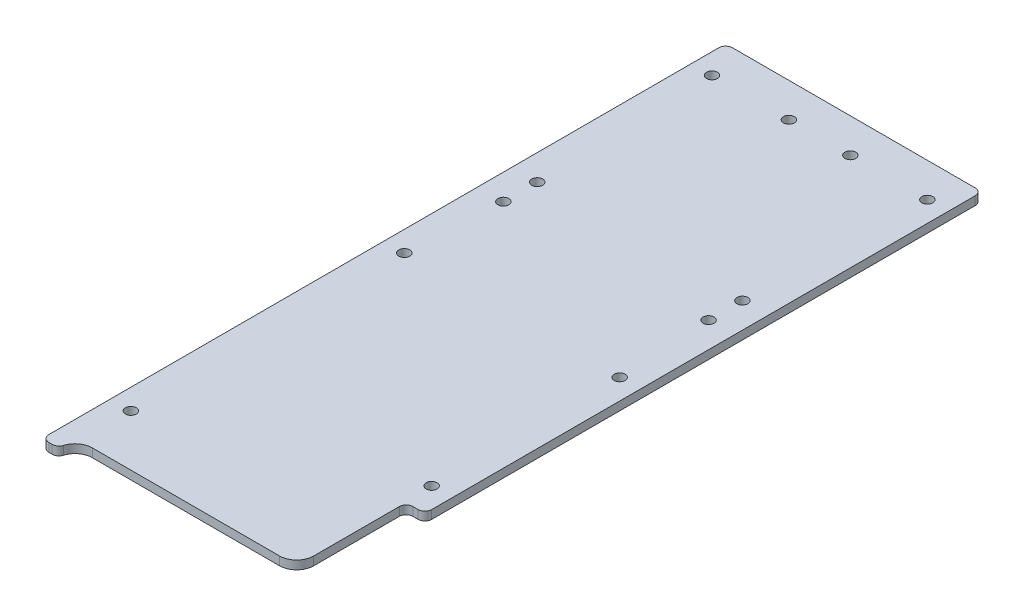
SolidWorks part; units mm, degrees
ref_plane "Front Plane" through (0, 0, 0) normal (0, 0, 1) x (1, 0, 0)
ref_plane "Top Plane" through (0, 0, 0) normal (0, 1, 0) x (1, 0, 0)
ref_plane "Right Plane" through (0, 0, 0) normal (1, 0, 0) x (0, 0, -1)
sketch "Sketch1" plane through (0, 0, 0) normal (0, 1, 0) x (1, 0, 0)
  line L0 (-39.9997, 0) -> (-39.9997, 114.3) construction
  line L1 (-47.625, 127) -> (47.625, 127)
  line L2 (-47.625, 127) -> (-47.625, -127)
  line L3 (-47.625, -127) -> (47.625, -127)
  line L4 (47.625, 127) -> (47.625, -127)
  line L5 (-47.625, 127) -> (47.625, -127) construction
  line L6 (-47.625, -127) -> (47.625, 127) construction
  line L7 (0, 0) -> (0, 127) construction
  line L8 (-39.9997, 0) -> (-39.9997, -101.6) construction
  line L9 (-39.9997, 0) -> (0, 0) construction
  line L10 (-41.275, -127) -> (-41.275, -120.65)
  line L11 (-41.275, -120.65) -> (41.275, -120.65)
  line L12 (41.275, -120.65) -> (41.275, -127)
  line L13 (-39.9997, 114.3) -> (-11.4247, 114.3) construction
  line L14 (39.9997, 114.3) -> (11.4247, 114.3) construction
  circle A0 centre (-39.9997, 114.3) radius 2.032
  circle A1 centre (-39.9997, 0) radius 2.032
  circle A2 centre (-39.9997, -101.6) radius 2.032
  circle A3 centre (39.9997, -101.6) radius 2.032
  circle A4 centre (39.9997, 0) radius 2.032
  circle A5 centre (39.9997, 114.3) radius 2.032
  circle A6 centre (-11.4247, 114.3) radius 2.032
  circle A7 centre (11.4247, 114.3) radius 2.032
  circle A8 centre (-39.9997, -69.85) radius 2.032
  circle A9 centre (39.9997, -69.85) radius 2.032
  point P0 (0, 0)
  dimension "D4" = 4.064
  dimension "D10" = 28.575
  dimension "D1" = 95.25
  dimension "D2" = 254
  dimension "D3" = 7.6253
  dimension "D5" = 12.7
  dimension "D6" = 25.4
  dimension "D7" = 6.35
  dimension "D8" = 6.35
  dimension "D9" = 6.35
  dimension "D11" = 69.85
extrude "Boss-Extrude1" add sketch "Sketch1" along normal blind 3.175 contours L4 L1 L2 L3 A4 A0 A1 A2 A3 A5 | A8 | A3 region at (0, 0, -2.6944) region at (39.9997, 0, 101.6) region at (-39.9997, 0, 69.85)
fillet "Fillet1" radius 2.54 4 edges at (-47.625, 1.5875, -127) (47.625, 1.5875, -127) (47.625, 1.5875, 127) (-47.625, 1.5875, 127)
fillet "Fillet2" radius 2.54 2 edges at (41.275, 1.5875, 127) (-41.275, 1.5875, 127)
fillet "Fillet3" radius 6.35 2 edges at (41.275, 1.5875, 120.65) (-41.275, 1.5875, 120.65)
sketch "Sketch2" plane through (0, 0, 0) normal (0, -1, 0) x (1, 0, 0)
  line L0 (41.9104, 131.8831) -> (41.9104, 109.8659) construction
  line L1 (41.9104, 109.8659) -> (41.9104, 106.3879) construction
  line L2 (41.9104, 83.271) -> (41.9104, 82.5325) construction
  line L3 (41.9104, 82.5325) -> (41.9104, 81.2514) construction
  line L4 (41.9104, 83.271) -> (41.9104, 106.3879) construction
  line L5 (41.9104, 131.8831) -> (41.9104, 109.8659)
  line L6 (41.9104, 109.8659) -> (41.9104, 106.3879)
  line L7 (41.9104, 83.271) -> (41.9104, 82.5325)
  line L8 (41.9104, 82.5325) -> (41.9104, 81.2514)
  line L9 (41.9104, 83.271) -> (41.9104, 106.3879)
  line L10 (41.9104, 81.2514) -> (47.625, 81.2514)
  line L11 (47.625, -124.46) -> (47.625, 124.46) construction
  line L12 (41.9104, 131.8831) -> (47.625, 131.8831)
  line L13 (47.625, 131.8831) -> (47.625, 81.2514)
  line L14 (40.6404, 79.9814) -> (48.895, 79.9814)
  line L15 (48.895, 133.1531) -> (48.895, 79.9814)
  line L16 (40.6404, 133.1531) -> (48.895, 133.1531)
  line L17 (40.6404, 133.1531) -> (40.6404, 109.8659)
  line L18 (40.6404, 109.8659) -> (40.6404, 106.3879)
  line L19 (40.6404, 83.271) -> (40.6404, 106.3879)
  line L20 (40.6404, 83.271) -> (40.6404, 82.5325)
  line L21 (40.6404, 82.5325) -> (40.6404, 79.9814)
  arc M7 (43.815, 127) -> (41.3809, 125.1857) centre (43.815, 124.46) ccw
  arc M8 (41.3809, 125.1857) -> (35.2956, 120.65) centre (35.2956, 127) cw
  line M18 (47.625, -124.46) -> (47.625, 124.46)
  dimension "D1" = 1.27
extrude "Cut-Extrude1" cut sketch "Sketch2" against normal through all contours L20 L21 L14 L10 L8 L7 L9 L19 M18 | L19 L9 L6 L5 L17 L18 M7 M8 | L13 L10 L8 L7 L9 L6 L5 L12 region at (41.6755, 0, 99.9793)
fillet "Fillet4" radius 6.35 1 edges at (40.6404, 1.5875, 123.5714)
fillet "Fillet5" radius 2.54 2 edges at (47.625, 1.5875, 79.9814) (40.6404, 1.5875, 79.9814)
sketch "Sketch3" plane through (0, 0, 0) normal (0, -1, 0) x (1, 0, 0)
  line L0 (-36.3101, -49.7791) -> (-39.9169, -49.7791) construction
  line L1 (-40.4249, -49.276) -> (-40.4249, -45.7043) construction
  line L2 (-35.8021, -45.7043) -> (-35.8021, -49.276) construction
  line L3 (-39.9169, -45.2013) -> (-36.3101, -45.2013) construction
  line L4 (-36.3101, -37.2027) -> (-39.9169, -37.2027) construction
  line L5 (-35.8021, -33.1279) -> (-35.8021, -36.6996) construction
  line L6 (-40.4249, -36.6996) -> (-40.4249, -33.1279) construction
  line L7 (-39.9169, -32.6249) -> (-36.3101, -32.6249) construction
  line L8 (36.2831, -32.6249) -> (39.8899, -32.6249) construction
  line L9 (40.3979, -33.1279) -> (40.3979, -36.6996) construction
  line L10 (39.8899, -37.2027) -> (36.2831, -37.2027) construction
  line L11 (35.7751, -36.6996) -> (35.7751, -33.1279) construction
  line L12 (36.2831, -45.2013) -> (39.8899, -45.2013) construction
  line L13 (35.7751, -49.276) -> (35.7751, -45.7043) construction
  line L14 (40.3979, -45.7043) -> (40.3979, -49.276) construction
  line L15 (39.8899, -49.7791) -> (36.2831, -49.7791) construction
  line L16 (-36.3101, -49.7791) -> (-39.9169, -49.7791)
  line L17 (-40.4249, -49.276) -> (-40.4249, -45.7043)
  line L18 (-35.8021, -45.7043) -> (-35.8021, -49.276)
  line L19 (-39.9169, -45.2013) -> (-36.3101, -45.2013)
  line L20 (-36.3101, -37.2027) -> (-39.9169, -37.2027)
  line L21 (-35.8021, -33.1279) -> (-35.8021, -36.6996)
  line L22 (-40.4249, -36.6996) -> (-40.4249, -33.1279)
  line L23 (-39.9169, -32.6249) -> (-36.3101, -32.6249)
  line L24 (36.2831, -32.6249) -> (39.8899, -32.6249)
  line L25 (40.3979, -33.1279) -> (40.3979, -36.6996)
  line L26 (39.8899, -37.2027) -> (36.2831, -37.2027)
  line L27 (35.7751, -36.6996) -> (35.7751, -33.1279)
  line L28 (36.2831, -45.2013) -> (39.8899, -45.2013)
  line L29 (35.7751, -49.276) -> (35.7751, -45.7043)
  line L30 (40.3979, -45.7043) -> (40.3979, -49.276)
  line L31 (39.8899, -49.7791) -> (36.2831, -49.7791)
  line L32 (-47.625, -25.836) -> (47.625, -25.836)
  line L33 (-47.625, -124.46) -> (-47.625, 124.46) construction
  line L34 (47.625, -124.46) -> (47.625, 77.4414) construction
  line L35 (0, -25.836) -> (0, -56.0686) construction
  line L38 (134.3607, -51.414) -> (184.1365, -51.414)
  line L39 (184.1365, -51.414) -> (184.1365, -43.4909)
  line L40 (184.1365, -43.4909) -> (182.3331, -43.4909)
  line L41 (181.8251, -42.9878) -> (181.8251, -39.4161)
  line L42 (182.3331, -38.9131) -> (184.1365, -38.9131)
  line L43 (184.1365, -38.9131) -> (184.1365, -30.9899)
  line L44 (184.1365, -30.9899) -> (134.3607, -30.9899)
  line L45 (134.3607, -30.9899) -> (133.3365, -32.0042)
  line L46 (133.3365, -32.0042) -> (132.3123, -30.9899)
  line L47 (132.3123, -30.9899) -> (70.8607, -30.9899)
  line L48 (70.8607, -30.9899) -> (69.8365, -32.0042)
  line L49 (69.8365, -32.0042) -> (68.8123, -30.9899)
  line L50 (68.8123, -30.9899) -> (7.3607, -30.9899)
  line L51 (7.3607, -30.9899) -> (6.3365, -32.0042)
  line L52 (6.3365, -32.0042) -> (5.3123, -30.9899)
  line L53 (5.3123, -30.9899) -> (-56.1393, -30.9899)
  line L54 (-56.1393, -30.9899) -> (-57.1635, -32.0042)
  line L55 (-57.1635, -32.0042) -> (-58.1877, -30.9899)
  line L56 (-58.1877, -30.9899) -> (-119.6393, -30.9899)
  line L57 (-119.6393, -30.9899) -> (-120.6635, -32.0042)
  line L58 (-120.6635, -32.0042) -> (-121.6877, -30.9899)
  line L59 (-121.6877, -30.9899) -> (-184.1635, -30.9899)
  line L60 (-184.1635, -30.9899) -> (-184.1635, -51.414)
  line L61 (-184.1635, -51.414) -> (-121.6877, -51.414)
  line L62 (-121.6877, -51.414) -> (-120.6635, -50.3998)
  line L63 (-120.6635, -50.3998) -> (-119.6393, -51.414)
  line L64 (-119.6393, -51.414) -> (-58.1877, -51.414)
  line L65 (-58.1877, -51.414) -> (-57.1635, -50.3998)
  line L66 (-57.1635, -50.3998) -> (-56.1393, -51.414)
  line L67 (-56.1393, -51.414) -> (5.3123, -51.414)
  line L68 (5.3123, -51.414) -> (6.3365, -50.3998)
  line L69 (6.3365, -50.3998) -> (7.3607, -51.414)
  line L70 (7.3607, -51.414) -> (68.8123, -51.414)
  line L71 (68.8123, -51.414) -> (69.8365, -50.3998)
  line L72 (69.8365, -50.3998) -> (70.8607, -51.414)
  line L73 (70.8607, -51.414) -> (132.3123, -51.414)
  line L74 (132.3123, -51.414) -> (133.3365, -50.3998)
  line L75 (133.3365, -50.3998) -> (134.3607, -51.414)
  line L76 (134.3607, -51.414) -> (184.1365, -51.414)
  line L77 (184.1365, -51.414) -> (184.1365, -43.4909)
  line L78 (184.1365, -43.4909) -> (182.3331, -43.4909)
  line L79 (181.8251, -42.9878) -> (181.8251, -39.4161)
  line L80 (182.3331, -38.9131) -> (184.1365, -38.9131)
  line L81 (184.1365, -38.9131) -> (184.1365, -30.9899)
  line L82 (184.1365, -30.9899) -> (134.3607, -30.9899)
  line L83 (134.3607, -30.9899) -> (133.3365, -32.0042)
  line L84 (133.3365, -32.0042) -> (132.3123, -30.9899)
  line L85 (132.3123, -30.9899) -> (70.8607, -30.9899)
  line L86 (70.8607, -30.9899) -> (69.8365, -32.0042)
  line L87 (69.8365, -32.0042) -> (68.8123, -30.9899)
  line L88 (68.8123, -30.9899) -> (7.3607, -30.9899)
  line L89 (7.3607, -30.9899) -> (6.3365, -32.0042)
  line L90 (6.3365, -32.0042) -> (5.3123, -30.9899)
  line L91 (5.3123, -30.9899) -> (-56.1393, -30.9899)
  line L92 (-56.1393, -30.9899) -> (-57.1635, -32.0042)
  line L93 (-57.1635, -32.0042) -> (-58.1877, -30.9899)
  line L94 (-58.1877, -30.9899) -> (-119.6393, -30.9899)
  line L95 (-119.6393, -30.9899) -> (-120.6635, -32.0042)
  line L96 (-120.6635, -32.0042) -> (-121.6877, -30.9899)
  line L97 (-121.6877, -30.9899) -> (-184.1635, -30.9899)
  line L98 (-184.1635, -30.9899) -> (-184.1635, -51.414)
  line L99 (-184.1635, -51.414) -> (-121.6877, -51.414)
  line L100 (-121.6877, -51.414) -> (-120.6635, -50.3998)
  line L101 (-120.6635, -50.3998) -> (-119.6393, -51.414)
  line L102 (-119.6393, -51.414) -> (-58.1877, -51.414)
  line L103 (-58.1877, -51.414) -> (-57.1635, -50.3998)
  line L104 (-57.1635, -50.3998) -> (-56.1393, -51.414)
  line L105 (-56.1393, -51.414) -> (5.3123, -51.414)
  line L106 (5.3123, -51.414) -> (6.3365, -50.3998)
  line L107 (6.3365, -50.3998) -> (7.3607, -51.414)
  line L108 (7.3607, -51.414) -> (68.8123, -51.414)
  line L109 (68.8123, -51.414) -> (69.8365, -50.3998)
  line L110 (69.8365, -50.3998) -> (70.8607, -51.414)
  line L111 (70.8607, -51.414) -> (132.3123, -51.414)
  line L112 (132.3123, -51.414) -> (133.3365, -50.3998)
  line L113 (133.3365, -50.3998) -> (134.3607, -51.414)
  line L1362 (-40.4249, -34.9138) -> (-35.8021, -34.9138)
  line L1857 (-38.1135, -32.6249) -> (-38.1135, -37.2027)
  line L1858 (-38.1135, -45.2013) -> (-38.1135, -49.7791)
  line L1859 (-40.4249, -47.4902) -> (-35.8021, -47.4902)
  circle A0 centre (-38.1135, -34.9138) radius 2.032
  circle A1 centre (-38.1135, -47.4902) radius 2.032
  circle A2 centre (38.1135, -47.4902) radius 2.032
  circle A3 centre (38.1135, -34.9138) radius 2.032
  ellipse E0 centre (-39.9169, -45.7043) end of major axis (-39.4089, -45.7043) minor radius 0.5031 (-39.9169, -45.2013) -> (-40.4249, -45.7043) ccw construction
  ellipse E1 centre (-39.9169, -49.276) end of major axis (-39.4089, -49.276) minor radius 0.5031 (-40.4249, -49.276) -> (-39.9169, -49.7791) ccw construction
  ellipse E2 centre (182.3331, -42.9878) end of major axis (182.8411, -42.9878) minor radius 0.5031 (181.8251, -42.9878) -> (182.3331, -43.4909) ccw
  ellipse E3 centre (182.3331, -39.4161) end of major axis (182.8411, -39.4161) minor radius 0.5031 (182.3331, -38.9131) -> (181.8251, -39.4161) ccw
  ellipse E4 centre (182.3331, -42.9878) end of major axis (182.8411, -42.9878) minor radius 0.5031 (181.8251, -42.9878) -> (182.3331, -43.4909) ccw
  ellipse E5 centre (182.3331, -39.4161) end of major axis (182.8411, -39.4161) minor radius 0.5031 (182.3331, -38.9131) -> (181.8251, -39.4161) ccw
  ellipse E6 centre (-36.3101, -49.276) end of major axis (-35.8021, -49.276) minor radius 0.5031 (-36.3101, -49.7791) -> (-35.8021, -49.276) ccw construction
  ellipse E7 centre (-36.3101, -45.7043) end of major axis (-35.8021, -45.7043) minor radius 0.5031 (-35.8021, -45.7043) -> (-36.3101, -45.2013) ccw construction
  ellipse E8 centre (-39.9169, -36.6996) end of major axis (-39.4089, -36.6996) minor radius 0.5031 (-40.4249, -36.6996) -> (-39.9169, -37.2027) ccw construction
  ellipse E9 centre (-36.3101, -36.6996) end of major axis (-35.8021, -36.6996) minor radius 0.5031 (-36.3101, -37.2027) -> (-35.8021, -36.6996) ccw construction
  ellipse E10 centre (-36.3101, -33.1279) end of major axis (-35.8021, -33.1279) minor radius 0.5031 (-35.8021, -33.1279) -> (-36.3101, -32.6249) ccw construction
  ellipse E11 centre (-39.9169, -33.1279) end of major axis (-39.4089, -33.1279) minor radius 0.5031 (-39.9169, -32.6249) -> (-40.4249, -33.1279) ccw construction
  ellipse E12 centre (39.8899, -33.1279) end of major axis (40.3979, -33.1279) minor radius 0.5031 (40.3979, -33.1279) -> (39.8899, -32.6249) ccw construction
  ellipse E13 centre (36.2831, -33.1279) end of major axis (36.7911, -33.1279) minor radius 0.5031 (36.2831, -32.6249) -> (35.7751, -33.1279) ccw construction
  ellipse E14 centre (39.8899, -36.6996) end of major axis (40.3979, -36.6996) minor radius 0.5031 (39.8899, -37.2027) -> (40.3979, -36.6996) ccw construction
  ellipse E15 centre (36.2831, -36.6996) end of major axis (36.7911, -36.6996) minor radius 0.5031 (35.7751, -36.6996) -> (36.2831, -37.2027) ccw construction
  ellipse E16 centre (36.2831, -45.7043) end of major axis (36.7911, -45.7043) minor radius 0.5031 (36.2831, -45.2013) -> (35.7751, -45.7043) ccw construction
  ellipse E17 centre (36.2831, -49.276) end of major axis (36.7911, -49.276) minor radius 0.5031 (35.7751, -49.276) -> (36.2831, -49.7791) ccw construction
  ellipse E18 centre (39.8899, -45.7043) end of major axis (40.3979, -45.7043) minor radius 0.5031 (40.3979, -45.7043) -> (39.8899, -45.2013) ccw construction
  ellipse E19 centre (39.8899, -49.276) end of major axis (40.3979, -49.276) minor radius 0.5031 (39.8899, -49.7791) -> (40.3979, -49.276) ccw construction
  ellipse E20 centre (-39.9169, -45.7043) end of major axis (-39.4089, -45.7043) minor radius 0.5031 (-39.9169, -45.2013) -> (-40.4249, -45.7043) ccw
  ellipse E21 centre (-39.9169, -49.276) end of major axis (-39.4089, -49.276) minor radius 0.5031 (-40.4249, -49.276) -> (-39.9169, -49.7791) ccw
  ellipse E22 centre (-36.3101, -49.276) end of major axis (-35.8021, -49.276) minor radius 0.5031 (-36.3101, -49.7791) -> (-35.8021, -49.276) ccw
  ellipse E23 centre (-36.3101, -45.7043) end of major axis (-35.8021, -45.7043) minor radius 0.5031 (-35.8021, -45.7043) -> (-36.3101, -45.2013) ccw
  ellipse E24 centre (-39.9169, -36.6996) end of major axis (-39.4089, -36.6996) minor radius 0.5031 (-40.4249, -36.6996) -> (-39.9169, -37.2027) ccw
  ellipse E25 centre (-36.3101, -36.6996) end of major axis (-35.8021, -36.6996) minor radius 0.5031 (-36.3101, -37.2027) -> (-35.8021, -36.6996) ccw
  ellipse E26 centre (-36.3101, -33.1279) end of major axis (-35.8021, -33.1279) minor radius 0.5031 (-35.8021, -33.1279) -> (-36.3101, -32.6249) ccw
  ellipse E27 centre (-39.9169, -33.1279) end of major axis (-39.4089, -33.1279) minor radius 0.5031 (-39.9169, -32.6249) -> (-40.4249, -33.1279) ccw
  ellipse E28 centre (39.8899, -33.1279) end of major axis (40.3979, -33.1279) minor radius 0.5031 (40.3979, -33.1279) -> (39.8899, -32.6249) ccw
  ellipse E29 centre (36.2831, -33.1279) end of major axis (36.7911, -33.1279) minor radius 0.5031 (36.2831, -32.6249) -> (35.7751, -33.1279) ccw
  ellipse E30 centre (39.8899, -36.6996) end of major axis (40.3979, -36.6996) minor radius 0.5031 (39.8899, -37.2027) -> (40.3979, -36.6996) ccw
  ellipse E31 centre (36.2831, -36.6996) end of major axis (36.7911, -36.6996) minor radius 0.5031 (35.7751, -36.6996) -> (36.2831, -37.2027) ccw
  ellipse E32 centre (36.2831, -45.7043) end of major axis (36.7911, -45.7043) minor radius 0.5031 (36.2831, -45.2013) -> (35.7751, -45.7043) ccw
  ellipse E33 centre (36.2831, -49.276) end of major axis (36.7911, -49.276) minor radius 0.5031 (35.7751, -49.276) -> (36.2831, -49.7791) ccw
  ellipse E34 centre (39.8899, -45.7043) end of major axis (40.3979, -45.7043) minor radius 0.5031 (40.3979, -45.7043) -> (39.8899, -45.2013) ccw
  ellipse E35 centre (39.8899, -49.276) end of major axis (40.3979, -49.276) minor radius 0.5031 (39.8899, -49.7791) -> (40.3979, -49.276) ccw
  dimension "D2" = 4.064
  dimension "D1" = 0
extrude "Cut-Extrude2" cut sketch "Sketch3" against normal through all contours A0 | A1 | A2 | A3
